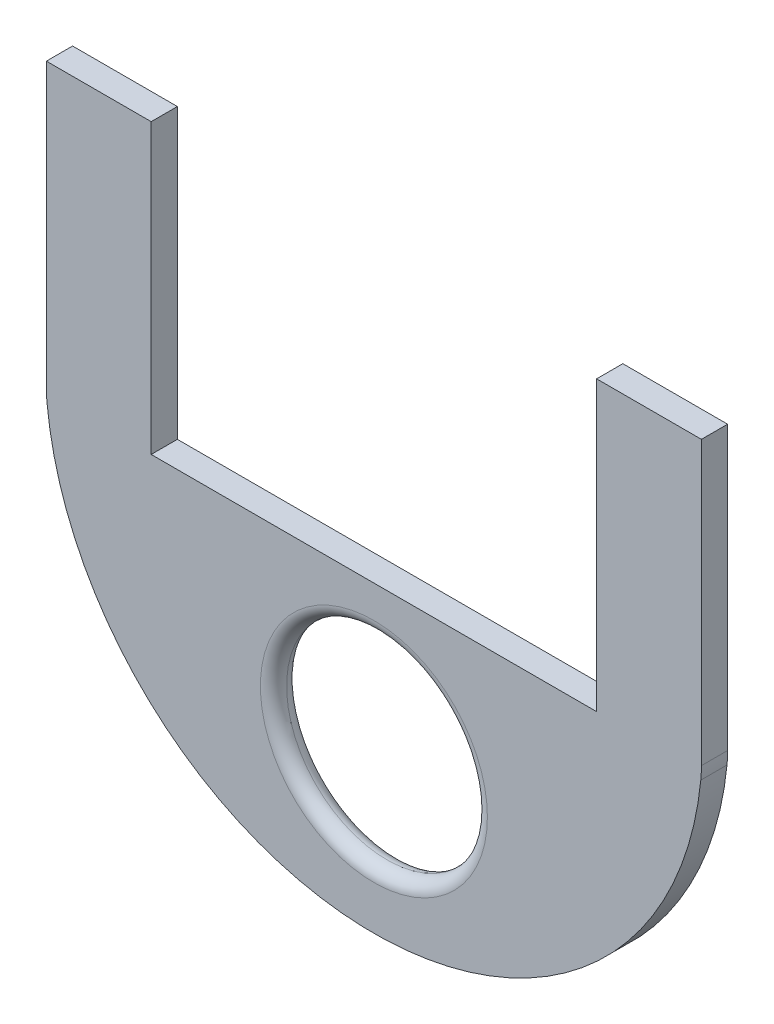
SolidWorks part; units mm, degrees
material "Plastique personnalisé"
ref_plane "Plan de face" through (0, 0, 0) normal (0, 0, 1) x (1, 0, 0)
ref_plane "Plan de dessus" through (0, 0, 0) normal (0, 1, 0) x (1, 0, 0)
ref_plane "Plan de droite" through (0, 0, 0) normal (1, 0, 0) x (0, 0, -1)
sketch "Esquisse1" plane through (0, 0, 0) normal (0, 0, 1) x (1, 0, 0)
  line L0 (0, 0) -> (34, 0)
  line L1 (34, 0) -> (34, 22)
  line L2 (0, 0) -> (0, 22)
  line L3 (0, 22) -> (-8, 22)
  line L4 (34, 22) -> (42, 22)
  line L5 (-8, 22) -> (-8, 0)
  line L6 (42, 22) -> (42, 0)
  line L7 (17, 0) -> (17, -31.2841) construction
  arc A4 (-8, 0) -> (42, 0) centre (17, 1.914) ccw
  circle A5 centre (17, -11.1359) radius 7.6638
  dimension "D1" = 34
  dimension "D2" = 22
  dimension "D3" = 8
  dimension "D4" = 8
extrude "Boss.-Extru.1" add sketch "Esquisse1" along normal blind 2
fillet "Congé1" radius 10 2 edges at (42, 0, 1) (-8, 0, 1)
fillet "Congé2" radius 1 2 edges at (24.6638, -11.1359, 0) (24.6638, -11.1359, 2)
